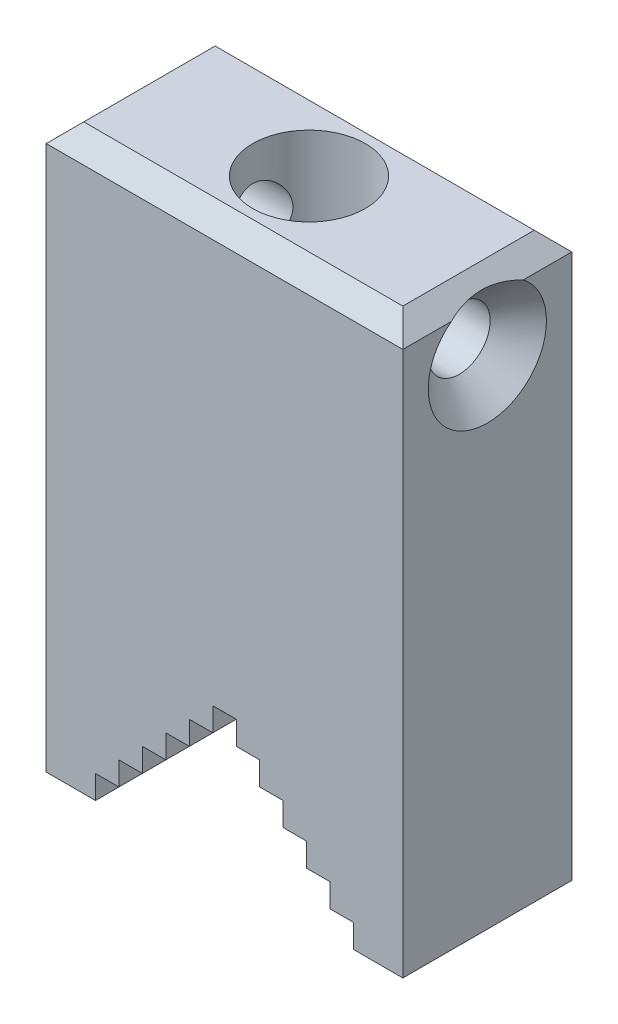
SolidWorks part; units mm, degrees
ref_plane "Front Plane" through (0, 0, 0) normal (0, 0, 1) x (1, 0, 0)
ref_plane "Top Plane" through (0, 0, 0) normal (0, 1, 0) x (1, 0, 0)
ref_plane "Right Plane" through (0, 0, 0) normal (1, 0, 0) x (0, 0, -1)
sketch "Sketch1" plane through (0, 0, 0) normal (0, 0, 1) x (1, 0, 0)
  line L0 (0, 0) -> (0, -35465.704) construction
  line L1 (0, 0) -> (35465.704, 0) construction
  line L2 (-19, 60) -> (-19, 0)
  line L3 (-19, 0) -> (19, 0)
  line L4 (19, 0) -> (19, 60)
  line L5 (19, 60) -> (-19, 60)
  line L7 (-13.75, 0) -> (13.75, 0)
  line L9 (-1.25, 15) -> (1.25, 15)
  line L10 (1.25, 15) -> (1.25, 12.5)
  line L11 (1.25, 12.5) -> (3.75, 12.5)
  line L12 (3.75, 12.5) -> (3.75, 10)
  line L13 (3.75, 10) -> (6.25, 10)
  line L14 (6.25, 10) -> (6.25, 7.5)
  line L15 (6.25, 7.5) -> (8.75, 7.5)
  line L16 (8.75, 7.5) -> (8.75, 5)
  line L17 (8.75, 5) -> (11.25, 5)
  line L18 (11.25, 5) -> (11.25, 2.5)
  line L19 (11.25, 2.5) -> (13.75, 2.5)
  line L20 (13.75, 2.5) -> (13.75, 0)
  line L21 (-1.25, 15) -> (-1.25, 12.5)
  line L22 (-1.25, 12.5) -> (-3.75, 12.5)
  line L23 (-13.75, 2.5) -> (-13.75, 0)
  line L24 (-11.25, 2.5) -> (-13.75, 2.5)
  line L25 (-11.25, 5) -> (-11.25, 2.5)
  line L26 (-8.75, 5) -> (-11.25, 5)
  line L27 (-8.75, 7.5) -> (-8.75, 5)
  line L28 (-6.25, 7.5) -> (-8.75, 7.5)
  line L29 (-6.25, 10) -> (-6.25, 7.5)
  line L30 (-3.75, 10) -> (-6.25, 10)
  line L31 (-3.75, 12.5) -> (-3.75, 10)
  line L32 (-13.75, 0) -> (1.25, 15) construction
  point P39 (0, 15)
  dimension "D1" = 38
  dimension "D2" = 60
  dimension "D3" = 2.5
  dimension "D4" = 27.5
  dimension "D5" = 45
  dimension "D6" = 2.5
extrude "Boss-Extrude1" add sketch "Sketch1" along normal mid plane 18 contours L31 L22 L21 L9 L10 L11 L12 L13 L14 L15 L16 L17 L18 L19 L20 L3 L4 L5 L2 L23 L24 L25 L26 L27 L28 L29 L30 region at (0, 32.7296, 0)
hole_wizard "Ø12.0mm Dowel Hole1" positions "Sketch8" profile "Sketch10" hole size "Ø12.0" standard "ANSI Metric"
sketch "Sketch8" plane through (0, 60, 0) normal (0, 1, 0) x (1, 0, 0)
  point P0 (0, 0)
sketch "Sketch10" plane through (0, 60, 0) normal (1, 0, 0) x (0, 0, 1)
  line L0 (0, 0) -> (0, 21.6052)
  line L1 (0, 21.6052) -> (6, 18)
  line L2 (6, 18) -> (6, 0)
  line L5 (6, 0) -> (0, 0)
  line L10 (0, 21.6052) -> (-6, 18) construction
  line L11 (0, -6.35) -> (0, 107.95) construction
  dimension "Hole Dia." = 12
  dimension "Hole Depth" = 18
  dimension "Drill Angle" = 118
hole_wizard "CSK for M6 Flat Head Machine Screw2" positions "Sketch11" profile "Sketch12" countersink size "M6" standard "ANSI Metric"
sketch "Sketch11" plane through (19, 0, 0) normal (1, 0, 0) x (0, 0, -1)
  line L0 (-9, 60) -> (9, 60) construction
  point P0 (0, 53)
  dimension "D1" = 7
sketch "Sketch12" plane through (19, 53, 0) normal (0, 1, 0) x (0, 0, -1)
  line L0 (0, 0) -> (0, 39.9828)
  line L1 (0, 39.9828) -> (3.3, 38)
  line L2 (3.3, 38) -> (3.3, 3)
  line L3 (3.3, 3) -> (6.3, 0)
  line L5 (6.3, 0) -> (0, 0)
  line L6 (-3.3, 3) -> (-6.3, 0) construction
  line L10 (0, 39.9828) -> (-3.3, 38) construction
  line L11 (0, -6.35) -> (0, 107.95) construction
  dimension "Hole Dia." = 6.6
  dimension "Hole Depth" = 38
  dimension "Near C'Sink Dia." = 12.6
  dimension "Near C'Sink Angle" = 90
  dimension "Drill Angle" = 118
chamfer "Chamfer1" distance 2 angle 45 4 edges at (19, 60, 0) (0, 60, 9) (-19, 60, 0) (0, 60, -9)
